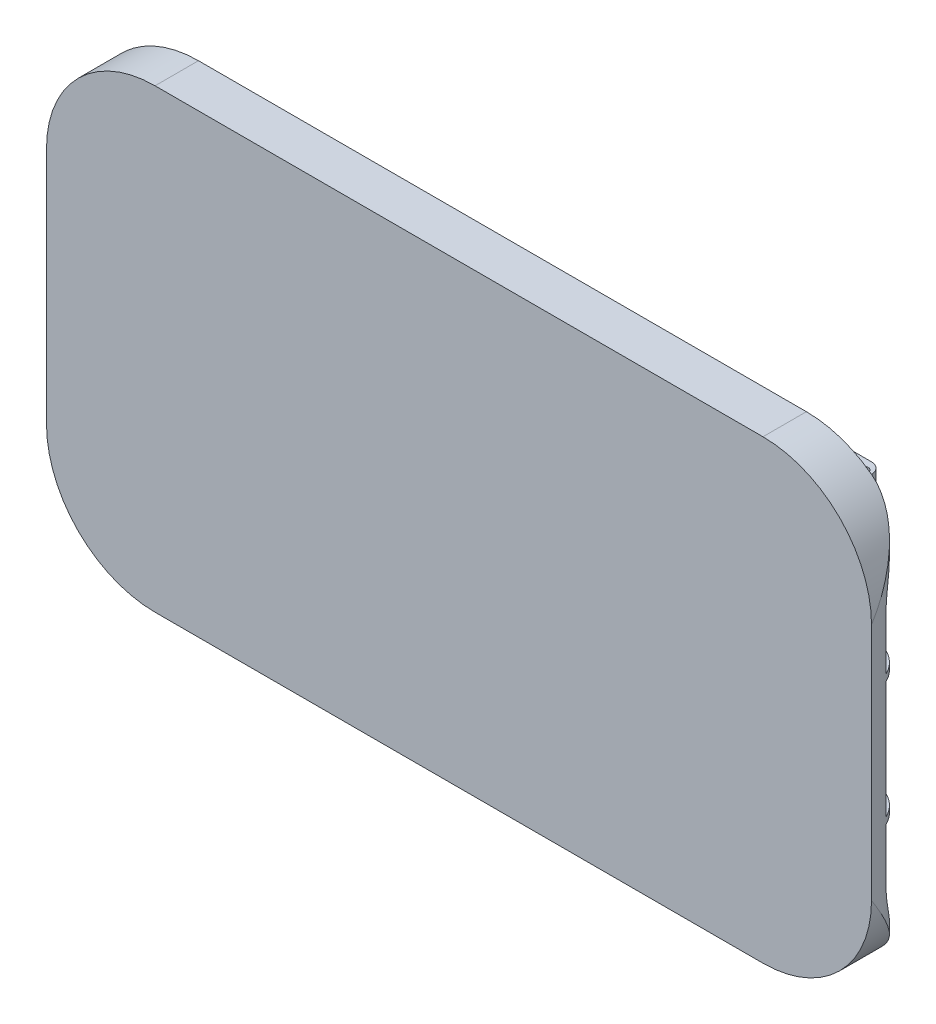
SolidWorks part; units mm, degrees
ref_plane "Front Plane" through (0, 0, 0) normal (0, 0, 1) x (1, 0, 0)
ref_plane "Top Plane" through (0, 0, 0) normal (0, 1, 0) x (1, 0, 0)
ref_plane "Right Plane" through (0, 0, 0) normal (1, 0, 0) x (0, 0, -1)
sketch "Sketch1" plane through (0, 0, 0) normal (0, 0, 1) x (1, 0, 0)
  line L1 (-190, 90) -> (190, 90)
  line L2 (-190, 90) -> (-190, -70)
  line L3 (-190, -70) -> (190, -70)
  line L4 (190, 90) -> (190, -70)
  dimension "D1" = 380
  dimension "D2" = 160
  dimension "D3" = 90
  dimension "D4" = 190
extrude "Boss-Extrude1" add sketch "Sketch1" along normal blind 3
sketch "Sketch3" plane through (0, -70, 0) normal (0, -1, 0) x (1, 0, 0)
  line L1 (-155, 3) -> (-130, 3)
  line L2 (-155, 3) -> (-155, -37)
  line L3 (-155, -37) -> (-130, -37)
  line L4 (-130, 3) -> (-130, -37)
  line L7 (-95, 0) -> (-95, -63.6731) construction
  line L8 (-60, 3) -> (-60, -37)
  line L9 (-35, -37) -> (-60, -37)
  line L10 (-35, 3) -> (-35, -37)
  line L11 (-35, 3) -> (-60, 3)
  line L12 (0, 0) -> (0, -25) construction
  line L13 (95, 0) -> (95, -63.6731) construction
  line L14 (35, 3) -> (60, 3)
  line L15 (35, 3) -> (35, -37)
  line L16 (35, -37) -> (60, -37)
  line L17 (60, 3) -> (60, -37)
  line L18 (130, 3) -> (130, -37)
  line L19 (155, -37) -> (130, -37)
  line L20 (155, 3) -> (155, -37)
  line L21 (155, 3) -> (130, 3)
  circle A0 centre (-151.5, -32) radius 2
  circle A1 centre (-133.5, -32) radius 2
  circle A2 centre (-56.5, -32) radius 2
  circle A3 centre (-38.5, -32) radius 2
  circle A4 centre (38.5, -32) radius 2
  circle A5 centre (56.5, -32) radius 2
  circle A6 centre (133.5, -32) radius 2
  circle A7 centre (151.5, -32) radius 2
  point P4 (0, 0)
  dimension "D4" = 35
  dimension "D8" = 35
  dimension "D3" = 35
  dimension "D1" = 25
  dimension "D2" = 40
  dimension "D9" = 35
extrude "Boss-Extrude2" add sketch "Sketch3" against normal blind 5
sketch "Sketch4" plane through (0, 90, 0) normal (0, 1, 0) x (1, 0, 0)
  line L4 (-155, -3) -> (-130, -3)
  line L5 (-130, -3) -> (-130, 37)
  line L6 (-130, 37) -> (-155, 37)
  line L7 (-155, 37) -> (-155, -3)
  line L8 (-155, -3) -> (-130, -3)
  line L9 (-130, -3) -> (-130, 37)
  line L10 (-130, 37) -> (-155, 37)
  line L11 (-155, 37) -> (-155, -3)
  line L12 (-60, 37) -> (-60, -3)
  line L13 (-35, 37) -> (-60, 37)
  line L14 (-35, -3) -> (-35, 37)
  line L15 (-60, -3) -> (-35, -3)
  line L16 (-60, 37) -> (-60, -3)
  line L17 (-35, 37) -> (-60, 37)
  line L18 (-35, -3) -> (-35, 37)
  line L19 (-60, -3) -> (-35, -3)
  line L20 (130, 37) -> (130, -3)
  line L21 (155, 37) -> (130, 37)
  line L22 (155, -3) -> (155, 37)
  line L23 (130, -3) -> (155, -3)
  line L24 (130, 37) -> (130, -3)
  line L25 (155, 37) -> (130, 37)
  line L26 (155, -3) -> (155, 37)
  line L27 (130, -3) -> (155, -3)
  line L28 (35, -3) -> (60, -3)
  line L29 (60, -3) -> (60, 37)
  line L30 (60, 37) -> (35, 37)
  line L31 (35, 37) -> (35, -3)
  line L32 (35, -3) -> (60, -3)
  line L33 (60, -3) -> (60, 37)
  line L34 (60, 37) -> (35, 37)
  line L35 (35, 37) -> (35, -3)
  circle A1 centre (-133.5, 32) radius 2
  circle A2 centre (-133.5, 32) radius 2
  circle A3 centre (-151.5, 32) radius 2
  circle A4 centre (-151.5, 32) radius 2
  circle A5 centre (56.5, 32) radius 2
  circle A6 centre (56.5, 32) radius 2
  circle A7 centre (38.5, 32) radius 2
  circle A8 centre (38.5, 32) radius 2
  circle A9 centre (-38.5, 32) radius 2
  circle A10 centre (-38.5, 32) radius 2
  circle A11 centre (-56.5, 32) radius 2
  circle A12 centre (-56.5, 32) radius 2
  circle A13 centre (151.5, 32) radius 2
  circle A14 centre (151.5, 32) radius 2
  circle A15 centre (133.5, 32) radius 2
  circle A16 centre (133.5, 32) radius 2
  dimension "D1" = 0
  dimension "D2" = 0
  dimension "D3" = 0
  dimension "D4" = 0
  dimension "D5" = 0
  dimension "D6" = 0
  dimension "D7" = 0
  dimension "D8" = 0
  dimension "D9" = 0
  dimension "D10" = 0
  dimension "D11" = 0
  dimension "D12" = 0
extrude "Boss-Extrude3" add sketch "Sketch4" against normal blind 5
fillet "Fillet1" radius 5 32 edges at (155, 87.5, 0) (130, 87.5, 0) (60, 87.5, 0) (35, 87.5, 0) (-60, 87.5, 0) (-35, 87.5, 0) (-130, 87.5, 0) (-155, 87.5, 0) (-155, -67.5, 0) (-130, -67.5, 0) (-35, -67.5, 0) (-60, -67.5, 0) (35, -67.5, 0) (60, -67.5, 0) (130, -67.5, 0) (155, -67.5, 0) (155, -67.5, -37) (130, -67.5, -37) (60, -67.5, -37) (35, -67.5, -37) (-35, -67.5, -37) (-60, -67.5, -37) (-130, -67.5, -37) (-155, -67.5, -37) (-155, 87.5, -37) (-130, 87.5, -37) (-35, 87.5, -37) (-60, 87.5, -37) (60, 87.5, -37) (35, 87.5, -37) (130, 87.5, -37) (155, 87.5, -37)
sketch "Sketch5" plane through (0, 0, 0) normal (0, 0, -1) x (-1, 0, 0)
  line L0 (142.5, -70) -> (142.5, 90) construction
  line L3 (47.5, -70) -> (47.5, 90) construction
  line L4 (55, -70) -> (40, -70) construction
  line L5 (40, 90) -> (55, 90) construction
  line L6 (150, -65) -> (135, -65) construction
  line L7 (144.5, -65) -> (140.5, -65)
  line L8 (144.5, -65) -> (144.5, 85)
  line L9 (144.5, 85) -> (140.5, 85)
  line L10 (140.5, -65) -> (140.5, 85)
  line L12 (135, 85) -> (150, 85) construction
  line L15 (150, -70) -> (135, -70) construction
  line L16 (135, 90) -> (150, 90) construction
  line L17 (55, -65) -> (40, -65) construction
  line L18 (49.5, -65) -> (45.5, -65)
  line L19 (49.5, -65) -> (49.5, 85)
  line L20 (49.5, 85) -> (45.5, 85)
  line L21 (45.5, -65) -> (45.5, 85)
  line L22 (40, 85) -> (55, 85) construction
  line L23 (0, 90) -> (0, -70) construction
  line L24 (-30, 90) -> (30, 90) construction
  line L25 (30, -70) -> (-30, -70) construction
  line L26 (-47.5, -70) -> (-47.5, 90) construction
  line L27 (-142.5, -70) -> (-142.5, 90) construction
  line L28 (-45.5, -65) -> (-45.5, 85)
  line L29 (-49.5, 85) -> (-45.5, 85)
  line L30 (-49.5, -65) -> (-49.5, 85)
  line L31 (-49.5, -65) -> (-45.5, -65)
  line L32 (-140.5, -65) -> (-140.5, 85)
  line L33 (-144.5, 85) -> (-140.5, 85)
  line L34 (-144.5, -65) -> (-144.5, 85)
  line L35 (-144.5, -65) -> (-140.5, -65)
  dimension "D1" = 0
  dimension "D2" = 2
  dimension "D3" = 2
  dimension "D4" = 2
  dimension "D5" = 2
extrude "Boss-Extrude4" add sketch "Sketch5" along normal blind 15
chamfer "Chamfer1" distance 7 angle 45 8 edges at (142.5, -65, -15) (47.5, -65, -15) (-47.5, -65, -15) (-142.5, -65, -15) (-142.5, 85, -15) (-47.5, 85, -15) (47.5, 85, -15) (142.5, 85, -15)
sketch "Sketch6" plane through (0, 0, 0) normal (0, 0, -1) x (-1, 0, 0)
  line L0 (190, 90) -> (190, -70) construction
  line L1 (190, -20) -> (-190, -20)
  line L2 (190, -20) -> (190, -17)
  line L3 (190, -17) -> (-190, -17)
  line L4 (-190, -20) -> (-190, -17)
  line L5 (-190, -70) -> (-190, 90) construction
  line L6 (160, 90) -> (190, 90) construction
  line L7 (-190, 37) -> (190, 37)
  line L8 (-190, 37) -> (-190, 40)
  line L9 (-190, 40) -> (190, 40)
  line L10 (190, 37) -> (190, 40)
  line L11 (190, -70) -> (160, -70) construction
  dimension "D1" = 3
  dimension "D2" = 50
  dimension "D3" = 3
  dimension "D4" = 50
extrude "Boss-Extrude5" add sketch "Sketch6" along normal blind 15
sketch "Sketch7" plane through (0, 0, 3) normal (0, 0, 1) x (1, 0, 0)
  line L0 (190, 90) -> (-190, 90) construction
  line L1 (-190, 115) -> (190, 115)
  line L2 (-190, 115) -> (-190, -95)
  line L3 (-190, -95) -> (190, -95)
  line L4 (190, 115) -> (190, -95)
  line L5 (-190, -70) -> (190, -70) construction
  point P10 (0, 0)
  dimension "D1" = 25
  dimension "D2" = 25
extrude "Boss-Extrude6" add sketch "Sketch7" against normal blind 3
fillet "Fillet3" radius 50 4 edges at (190, -95, 1.5) (190, 115, 1.5) (-190, 115, 1.5) (-190, -95, 1.5)
sketch "Sketch8" plane through (0, 0, 3) normal (0, 0, 1) x (1, 0, 0)
  line L0 (-140, -93) -> (140, -93)
  line L1 (188, -45) -> (188, 65)
  line L2 (140, 113) -> (-140, 113)
  line L3 (-188, 65) -> (-188, -45)
  line L4 (-140, -95) -> (140, -95)
  line L5 (190, -45) -> (190, 65)
  line L6 (140, 115) -> (-140, 115)
  line L7 (-190, 65) -> (-190, -45)
  line L8 (-140, -95) -> (140, -95)
  line L9 (190, -45) -> (190, 65)
  line L10 (140, 115) -> (-140, 115)
  line L11 (-190, 65) -> (-190, -45)
  arc A0 (140, -93) -> (188, -45) centre (140, -45) ccw
  arc A1 (188, 65) -> (140, 113) centre (140, 65) ccw
  arc A2 (-140, 113) -> (-188, 65) centre (-140, 65) ccw
  arc A3 (-188, -45) -> (-140, -93) centre (-140, -45) ccw
  arc A4 (140, -95) -> (190, -45) centre (140, -45) ccw
  arc A5 (190, 65) -> (140, 115) centre (140, 65) ccw
  arc A6 (-140, 115) -> (-190, 65) centre (-140, 65) ccw
  arc A7 (-190, -45) -> (-140, -95) centre (-140, -45) ccw
  arc A8 (140, -95) -> (190, -45) centre (140, -45) ccw
  arc A9 (190, 65) -> (140, 115) centre (140, 65) ccw
  arc A10 (-140, 115) -> (-190, 65) centre (-140, 65) ccw
  arc A11 (-190, -45) -> (-140, -95) centre (-140, -45) ccw
  dimension "D1" = 0
  dimension "D2" = 2
extrude "Boss-Extrude7" add sketch "Sketch8" against normal blind 20
sketch "Sketch9" plane through (0, -95, 0) normal (0, -1, 0) x (-1, 0, 0)
  line L0 (190, -3) -> (190, 17)
  line L1 (190, 17) -> (170, 17)
  line L2 (190, 17) -> (140, 17) construction
  line L3 (0, -3) -> (0, 28.5247) construction
  line L4 (140, -3) -> (-140, -3) construction
  line L5 (-190, 17) -> (-170, 17)
  line L6 (-190, -3) -> (-190, 17)
  arc A0 (190, -3) -> (170, 17) centre (170, -3) ccw
  arc A1 (-190, -3) -> (-170, 17) centre (-170, -3) cw
  dimension "D1" = 20
extrude "Cut-Extrude1" cut sketch "Sketch9" against normal through all
sketch "Sketch10" plane through (0, -20, 0) normal (0, -1, 0) x (1, 0, 0)
  line L1 (-170, -17) -> (-170, -15)
  line L2 (-188, -5.7178) -> (-188, 0) construction
  line L3 (-188, -5.7178) -> (-188, 0)
  line L4 (-186.2, -4.846) -> (-186.2, 0)
  line L5 (-144.5, 0) -> (-188, 0) construction
  line L6 (-186.2, 0) -> (-188, 0)
  arc A0 (-188, -5.7178) -> (-170, -17) centre (-170, 3) ccw construction
  arc A1 (-188, -5.7178) -> (-170, -17) centre (-170, 3) ccw
  arc A2 (-186.2, -4.846) -> (-170, -15) centre (-170, 3) ccw
  dimension "D1" = 2
extrude "Boss-Extrude10" add sketch "Sketch10" along normal up to surface and the other way up to surface up to face at (-164.014, -83.7027, -7.8383) other way up to face at (-164.014, 103.7027, -7.8383)
